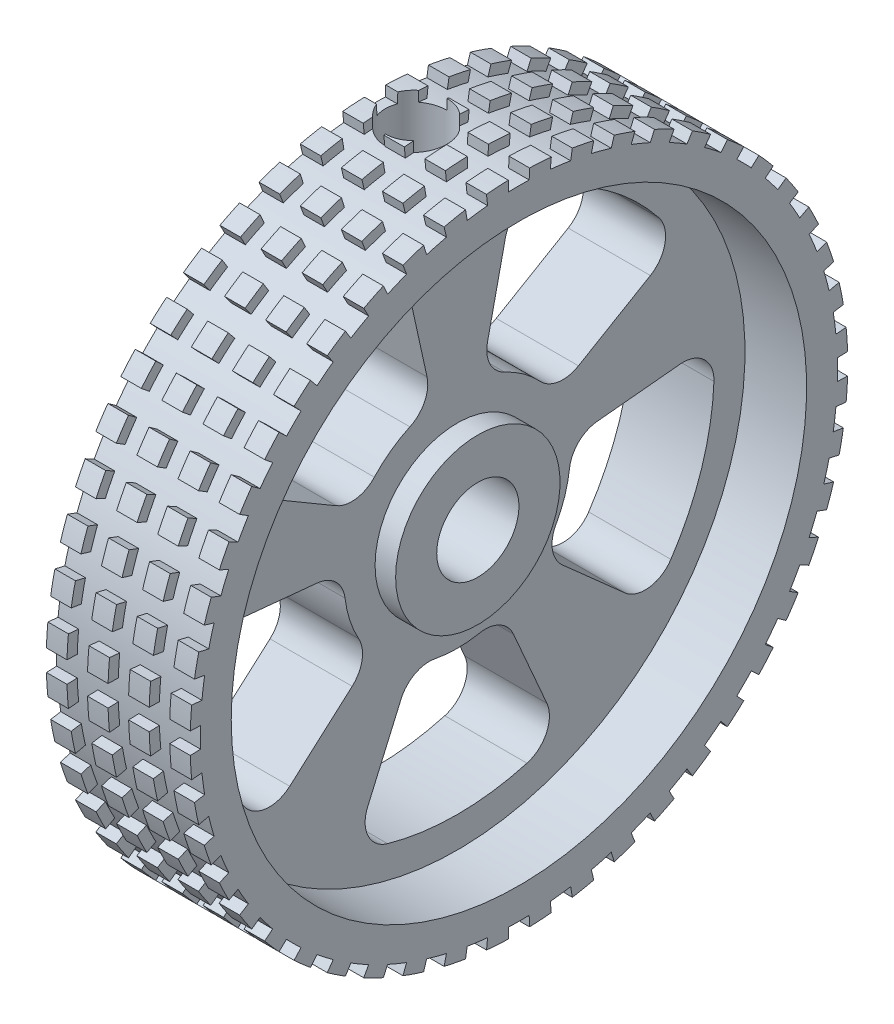
SolidWorks part; units mm, degrees
ref_plane "Front Plane" through (0, 0, 0) normal (0, 0, 1) x (1, 0, 0)
ref_plane "Top Plane" through (0, 0, 0) normal (0, 1, 0) x (1, 0, 0)
ref_plane "Right Plane" through (0, 0, 0) normal (1, 0, 0) x (0, 0, -1)
sketch "Sketch1" plane through (0, 0, 0) normal (0, 0, 1) x (1, 0, 0)
  line L0 (0, 0) -> (11.1229, 0) construction
  line L1 (0, 18.1419) -> (0, -13.4536) construction
  line L2 (0, 2) -> (5, 2)
  line L3 (0, 16) -> (7, 16)
  line L4 (4, 14) -> (7, 14)
  line L5 (0, 2) -> (0, 16)
  line L6 (5, 4) -> (4, 4)
  line L7 (4, 4) -> (4, 14)
  line L8 (7, 16) -> (7, 14)
  line L9 (5, 2) -> (5, 4)
  dimension "D1" = 4
  dimension "D2" = 7
  dimension "D3" = 4
  dimension "D4" = 8
  dimension "D5" = 5
  dimension "D6" = 32
  dimension "D7" = 28
revolve "Revolve1" add sketch "Sketch1" angle 360 about L0
sketch "Sketch2" plane through (0, 0, 0) normal (0, 0, 1) x (1, 0, 0)
  line L0 (0, 0) -> (6.2482, 0) construction
  line L1 (0, 16) -> (0, -16) construction
  line L2 (2, 0) -> (2, 17.4373) construction
  line L3 (2, 0) -> (2.9, 0)
  line L4 (2, 0) -> (2, 16)
  line L5 (7, 16) -> (0, 16) construction
  line L6 (2.9, 0) -> (2.9, 11.5)
  line L7 (2.9, 11.5) -> (3.5, 11.5)
  line L8 (3.5, 11.5) -> (3.5, 16)
  line L10 (2, 16) -> (3.5, 16)
  point P5 (3.2, 11.5)
  dimension "D1" = 1.8
  dimension "D2" = 4.5
  dimension "D3" = 2
revolve "Cut-Revolve1" cut sketch "Sketch2" angle 360 about L2
sketch "Sketch3" plane through (0, 0, 0) normal (0, 0, 1) x (1, 0, 0)
  line L0 (7, 16) -> (3.4999, 16) construction
  line L1 (5, 16) -> (6, 16)
  line L2 (5, 16) -> (5, 15.5)
  line L3 (5, 15.5) -> (6, 15.5)
  line L4 (6, 16) -> (6, 15.5)
  line L5 (7, -16) -> (7, 16) construction
  line L6 (0, 0) -> (5, 0) construction
  line L7 (0, 16) -> (0, -16) construction
  line L8 (5, -4) -> (5, 4) construction
  dimension "D1" = 0.5
  dimension "D2" = 1
  dimension "D3" = 1
revolve "Cut-Revolve2" cut sketch "Sketch3" angle 360 about L6
sketch "Sketch4" plane through (0, 0, 0) normal (1, 0, 0) x (0, 0, -1)
  line L0 (0, 0) -> (0, 16.9572) construction
  line L1 (0, 0) -> (-18.68, 0) construction
  line L2 (0.5156, 15.9917) -> (0.5, 15.4919)
  line L11 (-0.5156, 15.9917) -> (-0.5, 15.4919)
  circle A0 centre (0, 0) radius 16 construction
  arc A1 (0.5156, 15.9917) -> (-0.5156, 15.9917) centre (0, 0) ccw
  arc A2 (0.5, 15.4919) -> (-0.5, 15.4919) centre (0, 0) ccw
  point P3 (0, 15.7467)
  point P6 (-0.4878, 15.4924)
  point P7 (0.4782, 15.4924)
  dimension "D3" = 0.5
  dimension "D1" = 1
  dimension "D2" = 0.4998
extrude "Cut-Extrude3" cut sketch "Sketch4" along normal through all
pattern_circular "CirPattern2" count 48 over 360 about axis through (0, 0, 0) along (-1, 0, 0) of "Cut-Extrude3"
pattern_linear "LPattern1" count 3 spacing 2 along (-1, 0, 0) of "Cut-Revolve2"
sketch "Sketch6" plane through (4, 0, 0) normal (1, 0, 0) x (0, 0, -1)
  line L0 (0, 0) -> (0, 23.1418) construction
  line L1 (0, 0) -> (20.2388, 0) construction
  line L4 (-5, -11.4564) -> (-2.2, -5.0408)
  line L5 (5, -11.4564) -> (2.2, -5.0408)
  arc A4 (5, -11.4564) -> (-5, -11.4564) centre (0, 0) cw
  arc A5 (2.2, -5.0408) -> (-2.2, -5.0408) centre (0, 0) cw
  dimension "D1" = 7
  dimension "D2" = 47.156
  dimension "D5" = 12.5
  dimension "D3" = 6.4156
extrude "Cut-Extrude4" cut sketch "Sketch6" against normal through all
fillet "Fillet2" radius 1.5 4 edges at (2, -11.4564, -5) (2, -5.0408, 2.2) (2, -11.4564, 5) (2, -5.0408, -2.2)
pattern_circular "CirPattern3" count 5 over 360 about axis through (5, 0, 0) along (-1, 0, 0) of "Cut-Extrude4", "Fillet2"
